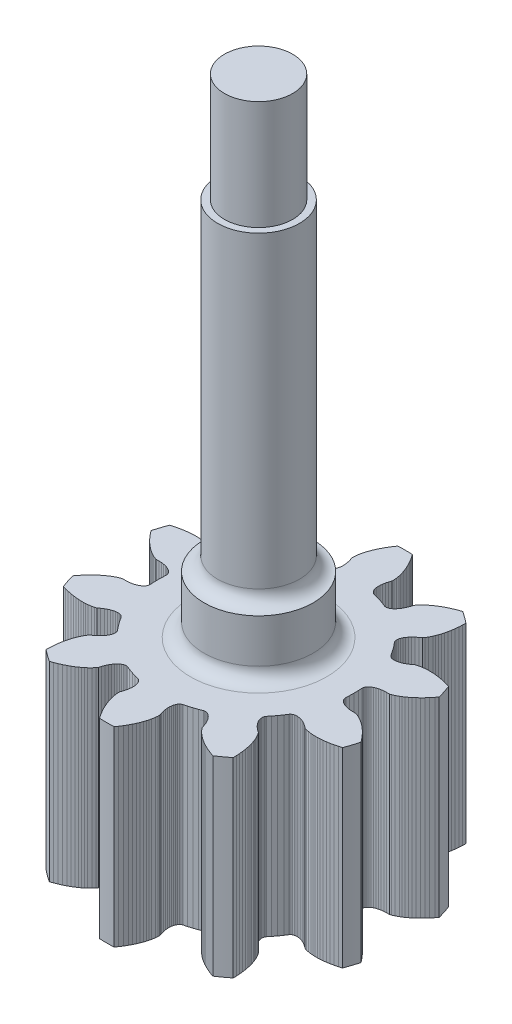
SolidWorks part; units mm, degrees
ref_plane "Front Plane" through (0, 0, 0) normal (0, 0, 1) x (1, 0, 0)
ref_plane "Top Plane" through (0, 0, 0) normal (0, 1, 0) x (1, 0, 0)
ref_plane "Right Plane" through (0, 0, 0) normal (1, 0, 0) x (0, 0, -1)
sketch "Sketch1" plane through (0, 0, 0) normal (0, 1, 0) x (1, 0, 0)
  circle A0 centre (0, 0) radius 2
  dimension "D1" = 4
extrude "Boss-Extrude1" add sketch "Sketch1" along normal blind 2.1
sketch "Sketch2" plane through (0, 2.1, 0) normal (0, 1, 0) x (1, 0, 0)
  circle A0 centre (0, 0) radius 1.5
  dimension "D1" = 3
extrude "Boss-Extrude3" add sketch "Sketch2" along normal blind 15.8
sketch "Sketch4" plane through (0, 0, 0) normal (0, -1, 0) x (1, 0, 0)
  line L0 (-3.5103, -4.1377) -> (-3.5022, -4.0065)
  line L1 (-3.5022, -4.0065) -> (-3.4891, -3.8807)
  line L2 (-3.4891, -3.8807) -> (-3.472, -3.7643)
  line L3 (-3.472, -3.7643) -> (-3.4515, -3.6564)
  line L4 (-3.4515, -3.6564) -> (-3.4282, -3.5564)
  line L5 (-3.4282, -3.5564) -> (-3.403, -3.4657)
  line L6 (-3.403, -3.4657) -> (-3.3761, -3.3825)
  line L7 (-3.3761, -3.3825) -> (-3.3483, -3.3075)
  line L8 (-3.3483, -3.3075) -> (-3.3202, -3.2404)
  line L9 (-3.3202, -3.2404) -> (-3.2664, -3.1313)
  line L10 (-3.2664, -3.1313) -> (-3.2183, -3.0513)
  line L11 (-3.2183, -3.0513) -> (-3.1781, -2.9961)
  line L12 (-3.1781, -2.9961) -> (-3.0986, -2.9414)
  line L13 (-3.0986, -2.9414) -> (-3.0227, -2.8808)
  line L14 (-3.0227, -2.8808) -> (-2.957, -2.8193)
  line L15 (-2.957, -2.8193) -> (-2.9016, -2.7578)
  line L16 (-2.9016, -2.7578) -> (-2.8562, -2.6969)
  line L17 (-2.8562, -2.6969) -> (-2.8208, -2.6373)
  line L18 (-2.8208, -2.6373) -> (-2.7951, -2.5799)
  line L19 (-2.7951, -2.5799) -> (-2.7789, -2.5252)
  line L20 (-2.7789, -2.5252) -> (-2.7718, -2.474)
  line L21 (-2.7718, -2.474) -> (-2.7736, -2.427)
  line L22 (-2.7736, -2.427) -> (-2.7838, -2.3847)
  line L23 (-2.7838, -2.3847) -> (-2.8021, -2.3479)
  line L24 (-2.8021, -2.3479) -> (-2.8109, -2.3356)
  line L25 (-2.8109, -2.3356) -> (-2.8974, -2.231)
  line L26 (-2.8974, -2.231) -> (-2.9943, -2.1036)
  line L27 (-2.9943, -2.1036) -> (-3.0855, -1.972)
  line L28 (-3.0855, -1.972) -> (-3.1583, -1.8575)
  line L29 (-3.1583, -1.8575) -> (-3.1673, -1.8453)
  line L30 (-3.1673, -1.8453) -> (-3.1967, -1.8165)
  line L31 (-3.1967, -1.8165) -> (-3.2337, -1.7937)
  line L32 (-3.2337, -1.7937) -> (-3.2779, -1.7775)
  line L33 (-3.2779, -1.7775) -> (-3.3287, -1.7684)
  line L34 (-3.3287, -1.7684) -> (-3.3857, -1.7669)
  line L35 (-3.3857, -1.7669) -> (-3.4483, -1.7736)
  line L36 (-3.4483, -1.7736) -> (-3.5159, -1.7889)
  line L37 (-3.5159, -1.7889) -> (-3.5879, -1.8132)
  line L38 (-3.5879, -1.8132) -> (-3.6635, -1.8469)
  line L39 (-3.6635, -1.8469) -> (-3.7423, -1.8903)
  line L40 (-3.7423, -1.8903) -> (-3.8234, -1.9438)
  line L41 (-3.8234, -1.9438) -> (-3.9, -2.0026)
  line L42 (-3.9, -2.0026) -> (-3.9648, -2.0237)
  line L43 (-3.9648, -2.0237) -> (-4.0558, -2.0448)
  line L44 (-4.0558, -2.0448) -> (-4.1762, -2.0622)
  line L45 (-4.1762, -2.0622) -> (-4.2487, -2.0682)
  line L46 (-4.2487, -2.0682) -> (-4.3286, -2.0714)
  line L47 (-4.3286, -2.0714) -> (-4.4161, -2.0713)
  line L48 (-4.4161, -2.0713) -> (-4.5101, -2.0673)
  line L49 (-4.5101, -2.0673) -> (-4.6124, -2.0586)
  line L50 (-4.6124, -2.0586) -> (-4.7214, -2.0447)
  line L51 (-4.7214, -2.0447) -> (-4.8374, -2.025)
  line L52 (-4.8374, -2.025) -> (-4.9611, -1.9985)
  line L53 (-4.9611, -1.9985) -> (-5.0883, -1.9657)
  line L54 (-5.0883, -1.9657) -> (-5.1999, -1.9322)
  line L55 (-5.3654, -1.4226) -> (-5.2949, -1.3299)
  line L56 (-5.2949, -1.3299) -> (-5.2112, -1.2286)
  line L57 (-5.2112, -1.2286) -> (-5.1267, -1.1345)
  line L58 (-5.1267, -1.1345) -> (-5.0445, -1.0503)
  line L59 (-5.0445, -1.0503) -> (-4.9645, -0.9751)
  line L60 (-4.9645, -0.9751) -> (-4.8868, -0.9079)
  line L61 (-4.8868, -0.9079) -> (-4.8131, -0.8494)
  line L62 (-4.8131, -0.8494) -> (-4.7424, -0.7978)
  line L63 (-4.7424, -0.7978) -> (-4.6759, -0.7535)
  line L64 (-4.6759, -0.7535) -> (-4.6137, -0.7157)
  line L65 (-4.6137, -0.7157) -> (-4.5061, -0.6591)
  line L66 (-4.5061, -0.6591) -> (-4.4201, -0.6226)
  line L67 (-4.4201, -0.6226) -> (-4.3552, -0.6016)
  line L68 (-4.3552, -0.6016) -> (-4.2587, -0.6041)
  line L69 (-4.2587, -0.6041) -> (-4.1616, -0.5997)
  line L70 (-4.1616, -0.5997) -> (-4.0724, -0.5886)
  line L71 (-4.0724, -0.5886) -> (-3.9914, -0.5713)
  line L72 (-3.9914, -0.5713) -> (-3.9189, -0.5487)
  line L73 (-3.9189, -0.5487) -> (-3.8552, -0.5213)
  line L74 (-3.8552, -0.5213) -> (-3.8007, -0.49)
  line L75 (-3.8007, -0.49) -> (-3.7554, -0.4553)
  line L76 (-3.7554, -0.4553) -> (-3.7196, -0.418)
  line L77 (-3.7196, -0.418) -> (-3.6934, -0.379)
  line L78 (-3.6934, -0.379) -> (-3.6768, -0.3388)
  line L79 (-3.6768, -0.3388) -> (-3.6699, -0.2982)
  line L80 (-3.6699, -0.2982) -> (-3.6699, -0.283)
  line L81 (-3.6699, -0.283) -> (-3.6783, -0.1476)
  line L82 (-3.6783, -0.1476) -> (-3.6819, 0.0124)
  line L83 (-3.6819, 0.0124) -> (-3.6783, 0.1725)
  line L84 (-3.6783, 0.1725) -> (-3.6699, 0.3079)
  line L85 (-3.6699, 0.3079) -> (-3.6699, 0.3231)
  line L86 (-3.6699, 0.3231) -> (-3.6768, 0.3636)
  line L87 (-3.6768, 0.3636) -> (-3.6934, 0.4038)
  line L88 (-3.6934, 0.4038) -> (-3.7196, 0.4429)
  line L89 (-3.7196, 0.4429) -> (-3.7554, 0.4802)
  line L90 (-3.7554, 0.4802) -> (-3.8007, 0.5149)
  line L91 (-3.8007, 0.5149) -> (-3.8552, 0.5462)
  line L92 (-3.8552, 0.5462) -> (-3.9189, 0.5736)
  line L93 (-3.9189, 0.5736) -> (-3.9914, 0.5962)
  line L94 (-3.9914, 0.5962) -> (-4.0724, 0.6134)
  line L95 (-4.0724, 0.6134) -> (-4.1616, 0.6246)
  line L96 (-4.1616, 0.6246) -> (-4.2587, 0.629)
  line L97 (-4.2587, 0.629) -> (-4.3552, 0.6265)
  line L98 (-4.3552, 0.6265) -> (-4.4201, 0.6475)
  line L99 (-4.4201, 0.6475) -> (-4.5061, 0.684)
  line L100 (-4.5061, 0.684) -> (-4.6137, 0.7406)
  line L101 (-4.6137, 0.7406) -> (-4.6759, 0.7784)
  line L102 (-4.6759, 0.7784) -> (-4.7424, 0.8227)
  line L103 (-4.7424, 0.8227) -> (-4.8131, 0.8742)
  line L104 (-4.8131, 0.8742) -> (-4.8868, 0.9328)
  line L105 (-4.8868, 0.9328) -> (-4.9645, 0.9999)
  line L106 (-4.9645, 0.9999) -> (-5.0445, 1.0752)
  line L107 (-5.0445, 1.0752) -> (-5.1267, 1.1594)
  line L108 (-5.1267, 1.1594) -> (-5.2112, 1.2535)
  line L109 (-5.2112, 1.2535) -> (-5.2949, 1.3548)
  line L110 (-5.2949, 1.3548) -> (-5.3654, 1.4475)
  line L111 (-5.1999, 1.957) -> (-5.0883, 1.9906)
  line L112 (-5.0883, 1.9906) -> (-4.9611, 2.0234)
  line L113 (-4.9611, 2.0234) -> (-4.8374, 2.0499)
  line L114 (-4.8374, 2.0499) -> (-4.7214, 2.0696)
  line L115 (-4.7214, 2.0696) -> (-4.6124, 2.0835)
  line L116 (-4.6124, 2.0835) -> (-4.5101, 2.0922)
  line L117 (-4.5101, 2.0922) -> (-4.4161, 2.0962)
  line L118 (-4.4161, 2.0962) -> (-4.3286, 2.0963)
  line L119 (-4.3286, 2.0963) -> (-4.2487, 2.0931)
  line L120 (-4.2487, 2.0931) -> (-4.1762, 2.0871)
  line L121 (-4.1762, 2.0871) -> (-4.0558, 2.0696)
  line L122 (-4.0558, 2.0696) -> (-3.9648, 2.0486)
  line L123 (-3.9648, 2.0486) -> (-3.9, 2.0274)
  line L124 (-3.9, 2.0274) -> (-3.8234, 1.9687)
  line L125 (-3.8234, 1.9687) -> (-3.7423, 1.9152)
  line L126 (-3.7423, 1.9152) -> (-3.6635, 1.8718)
  line L127 (-3.6635, 1.8718) -> (-3.5879, 1.8381)
  line L128 (-3.5879, 1.8381) -> (-3.5159, 1.8138)
  line L129 (-3.5159, 1.8138) -> (-3.4483, 1.7985)
  line L130 (-3.4483, 1.7985) -> (-3.3857, 1.7918)
  line L131 (-3.3857, 1.7918) -> (-3.3287, 1.7933)
  line L132 (-3.3287, 1.7933) -> (-3.2779, 1.8024)
  line L133 (-3.2779, 1.8024) -> (-3.2337, 1.8186)
  line L134 (-3.2337, 1.8186) -> (-3.1967, 1.8414)
  line L135 (-3.1967, 1.8414) -> (-3.1673, 1.8702)
  line L136 (-3.1673, 1.8702) -> (-3.1583, 1.8824)
  line L137 (-3.1583, 1.8824) -> (-3.0855, 1.9969)
  line L138 (-3.0855, 1.9969) -> (-2.9943, 2.1285)
  line L139 (-2.9943, 2.1285) -> (-2.8974, 2.2559)
  line L140 (-2.8974, 2.2559) -> (-2.8109, 2.3605)
  line L141 (-2.8109, 2.3605) -> (-2.8021, 2.3728)
  line L142 (-2.8021, 2.3728) -> (-2.7838, 2.4096)
  line L143 (-2.7838, 2.4096) -> (-2.7736, 2.4519)
  line L144 (-2.7736, 2.4519) -> (-2.7718, 2.4989)
  line L145 (-2.7718, 2.4989) -> (-2.7789, 2.5501)
  line L146 (-2.7789, 2.5501) -> (-2.7951, 2.6048)
  line L147 (-2.7951, 2.6048) -> (-2.8208, 2.6622)
  line L148 (-2.8208, 2.6622) -> (-2.8562, 2.7218)
  line L149 (-2.8562, 2.7218) -> (-2.9016, 2.7827)
  line L150 (-2.9016, 2.7827) -> (-2.957, 2.8442)
  line L151 (-2.957, 2.8442) -> (-3.0227, 2.9057)
  line L152 (-3.0227, 2.9057) -> (-3.0986, 2.9663)
  line L153 (-3.0986, 2.9663) -> (-3.1781, 3.021)
  line L154 (-3.1781, 3.021) -> (-3.2183, 3.0762)
  line L155 (-3.2183, 3.0762) -> (-3.2664, 3.1562)
  line L156 (-3.2664, 3.1562) -> (-3.3202, 3.2653)
  line L157 (-3.3202, 3.2653) -> (-3.3483, 3.3324)
  line L158 (-3.3483, 3.3324) -> (-3.3761, 3.4074)
  line L159 (-3.3761, 3.4074) -> (-3.403, 3.4906)
  line L160 (-3.403, 3.4906) -> (-3.4282, 3.5812)
  line L161 (-3.4282, 3.5812) -> (-3.4515, 3.6813)
  line L162 (-3.4515, 3.6813) -> (-3.472, 3.7892)
  line L163 (-3.472, 3.7892) -> (-3.4891, 3.9056)
  line L164 (-3.4891, 3.9056) -> (-3.5022, 4.0314)
  line L165 (-3.5022, 4.0314) -> (-3.5103, 4.1625)
  line L166 (-3.5103, 4.1625) -> (-3.5128, 4.279)
  line L167 (-3.0794, 4.5939) -> (-2.9694, 4.5555)
  line L168 (-2.9694, 4.5555) -> (-2.8472, 4.5073)
  line L169 (-2.8472, 4.5073) -> (-2.7316, 4.456)
  line L170 (-2.7316, 4.456) -> (-2.6261, 4.4037)
  line L171 (-2.6261, 4.4037) -> (-2.5298, 4.3509)
  line L172 (-2.5298, 4.3509) -> (-2.4419, 4.2978)
  line L173 (-2.4419, 4.2978) -> (-2.3635, 4.2458)
  line L174 (-2.3635, 4.2458) -> (-2.2927, 4.1945)
  line L175 (-2.2927, 4.1945) -> (-2.23, 4.1449)
  line L176 (-2.23, 4.1449) -> (-2.1748, 4.0974)
  line L177 (-2.1748, 4.0974) -> (-2.0877, 4.0126)
  line L178 (-2.0877, 4.0126) -> (-2.0264, 3.9421)
  line L179 (-2.0264, 3.9421) -> (-1.9864, 3.8869)
  line L180 (-1.9864, 3.8869) -> (-1.9589, 3.7943)
  line L181 (-1.9589, 3.7943) -> (-1.9248, 3.7034)
  line L182 (-1.9248, 3.7034) -> (-1.8866, 3.6219)
  line L183 (-1.8866, 3.6219) -> (-1.8452, 3.5502)
  line L184 (-1.8452, 3.5502) -> (-1.8012, 3.4883)
  line L185 (-1.8012, 3.4883) -> (-1.7556, 3.4362)
  line L186 (-1.7556, 3.4362) -> (-1.7089, 3.394)
  line L187 (-1.7089, 3.394) -> (-1.6619, 3.3616)
  line L188 (-1.6619, 3.3616) -> (-1.6154, 3.3391)
  line L189 (-1.6154, 3.3391) -> (-1.5701, 3.3262)
  line L190 (-1.5701, 3.3262) -> (-1.5268, 3.3229)
  line L191 (-1.5268, 3.3229) -> (-1.4861, 3.3289)
  line L192 (-1.4861, 3.3289) -> (-1.4716, 3.3335)
  line L193 (-1.4716, 3.3335) -> (-1.3455, 3.3834)
  line L194 (-1.3455, 3.3834) -> (-1.1943, 3.4362)
  line L195 (-1.1943, 3.4362) -> (-1.041, 3.4823)
  line L196 (-1.041, 3.4823) -> (-0.9096, 3.5161)
  line L197 (-0.9096, 3.5161) -> (-0.8952, 3.5209)
  line L198 (-0.8952, 3.5209) -> (-0.8588, 3.54)
  line L199 (-0.8588, 3.54) -> (-0.8256, 3.5681)
  line L200 (-0.8256, 3.5681) -> (-0.7966, 3.6051)
  line L201 (-0.7966, 3.6051) -> (-0.7722, 3.6507)
  line L202 (-0.7722, 3.6507) -> (-0.7532, 3.7045)
  line L203 (-0.7532, 3.7045) -> (-0.7402, 3.7661)
  line L204 (-0.7402, 3.7661) -> (-0.7339, 3.8351)
  line L205 (-0.7339, 3.8351) -> (-0.7348, 3.911)
  line L206 (-0.7348, 3.911) -> (-0.7434, 3.9934)
  line L207 (-0.7434, 3.9934) -> (-0.7604, 4.0817)
  line L208 (-0.7604, 4.0817) -> (-0.7862, 4.1753)
  line L209 (-0.7862, 4.1753) -> (-0.8184, 4.2664)
  line L210 (-0.8184, 4.2664) -> (-0.8185, 4.3346)
  line L211 (-0.8185, 4.3346) -> (-0.8104, 4.4276)
  line L212 (-0.8104, 4.4276) -> (-0.7898, 4.5475)
  line L213 (-0.7898, 4.5475) -> (-0.773, 4.6183)
  line L214 (-0.773, 4.6183) -> (-0.7514, 4.6953)
  line L215 (-0.7514, 4.6953) -> (-0.7243, 4.7785)
  line L216 (-0.7243, 4.7785) -> (-0.6914, 4.8666)
  line L217 (-0.6914, 4.8666) -> (-0.6515, 4.9612)
  line L218 (-0.6515, 4.9612) -> (-0.6047, 5.0605)
  line L219 (-0.6047, 5.0605) -> (-0.55, 5.1648)
  line L220 (-0.55, 5.1648) -> (-0.4867, 5.2743)
  line L221 (-0.4867, 5.2743) -> (-0.4161, 5.3851)
  line L222 (-0.4161, 5.3851) -> (-0.3498, 5.4809)
  line L223 (0.186, 5.4809) -> (0.2524, 5.3851)
  line L224 (0.2524, 5.3851) -> (0.3229, 5.2743)
  line L225 (0.3229, 5.2743) -> (0.3863, 5.1648)
  line L226 (0.3863, 5.1648) -> (0.4409, 5.0605)
  line L227 (0.4409, 5.0605) -> (0.4878, 4.9612)
  line L228 (0.4878, 4.9612) -> (0.5277, 4.8666)
  line L229 (0.5277, 4.8666) -> (0.5605, 4.7785)
  line L230 (0.5605, 4.7785) -> (0.5877, 4.6953)
  line L231 (0.5877, 4.6953) -> (0.6093, 4.6183)
  line L232 (0.6093, 4.6183) -> (0.626, 4.5475)
  line L233 (0.626, 4.5475) -> (0.6466, 4.4276)
  line L234 (0.6466, 4.4276) -> (0.6547, 4.3346)
  line L235 (0.6547, 4.3346) -> (0.6546, 4.2664)
  line L236 (0.6546, 4.2664) -> (0.6224, 4.1753)
  line L237 (0.6224, 4.1753) -> (0.5967, 4.0817)
  line L238 (0.5967, 4.0817) -> (0.5797, 3.9934)
  line L239 (0.5797, 3.9934) -> (0.571, 3.911)
  line L240 (0.571, 3.911) -> (0.5702, 3.8351)
  line L241 (0.5702, 3.8351) -> (0.5765, 3.7661)
  line L242 (0.5765, 3.7661) -> (0.5895, 3.7045)
  line L243 (0.5895, 3.7045) -> (0.6085, 3.6507)
  line L244 (0.6085, 3.6507) -> (0.6328, 3.6051)
  line L245 (0.6328, 3.6051) -> (0.6619, 3.5681)
  line L246 (0.6619, 3.5681) -> (0.695, 3.54)
  line L247 (0.695, 3.54) -> (0.7315, 3.5209)
  line L248 (0.7315, 3.5209) -> (0.7459, 3.5161)
  line L249 (0.7459, 3.5161) -> (0.8773, 3.4823)
  line L250 (0.8773, 3.4823) -> (1.0306, 3.4362)
  line L251 (1.0306, 3.4362) -> (1.1817, 3.3834)
  line L252 (1.1817, 3.3834) -> (1.3079, 3.3335)
  line L253 (1.3079, 3.3335) -> (1.3223, 3.3289)
  line L254 (1.3223, 3.3289) -> (1.363, 3.3229)
  line L255 (1.363, 3.3229) -> (1.4064, 3.3262)
  line L256 (1.4064, 3.3262) -> (1.4517, 3.3391)
  line L257 (1.4517, 3.3391) -> (1.4982, 3.3616)
  line L258 (1.4982, 3.3616) -> (1.5451, 3.394)
  line L259 (1.5451, 3.394) -> (1.5918, 3.4362)
  line L260 (1.5918, 3.4362) -> (1.6375, 3.4883)
  line L261 (1.6375, 3.4883) -> (1.6814, 3.5502)
  line L262 (1.6814, 3.5502) -> (1.7229, 3.6219)
  line L263 (1.7229, 3.6219) -> (1.761, 3.7034)
  line L264 (1.761, 3.7034) -> (1.7952, 3.7943)
  line L265 (1.7952, 3.7943) -> (1.8227, 3.8869)
  line L266 (1.8227, 3.8869) -> (1.8627, 3.9421)
  line L267 (1.8627, 3.9421) -> (1.9239, 4.0126)
  line L268 (1.9239, 4.0126) -> (2.0111, 4.0974)
  line L269 (2.0111, 4.0974) -> (2.0662, 4.1449)
  line L270 (2.0662, 4.1449) -> (2.1289, 4.1945)
  line L271 (2.1289, 4.1945) -> (2.1998, 4.2458)
  line L272 (2.1998, 4.2458) -> (2.2782, 4.2978)
  line L273 (2.2782, 4.2978) -> (2.3661, 4.3509)
  line L274 (2.3661, 4.3509) -> (2.4624, 4.4037)
  line L275 (2.4624, 4.4037) -> (2.5679, 4.456)
  line L276 (2.5679, 4.456) -> (2.6835, 4.5073)
  line L277 (2.6835, 4.5073) -> (2.8057, 4.5555)
  line L278 (2.8057, 4.5555) -> (2.9157, 4.5939)
  line L279 (3.3491, 4.279) -> (3.3465, 4.1625)
  line L280 (3.3465, 4.1625) -> (3.3384, 4.0314)
  line L281 (3.3384, 4.0314) -> (3.3254, 3.9056)
  line L282 (3.3254, 3.9056) -> (3.3083, 3.7892)
  line L283 (3.3083, 3.7892) -> (3.2878, 3.6813)
  line L284 (3.2878, 3.6813) -> (3.2644, 3.5812)
  line L285 (3.2644, 3.5812) -> (3.2392, 3.4906)
  line L286 (3.2392, 3.4906) -> (3.2123, 3.4074)
  line L287 (3.2123, 3.4074) -> (3.1846, 3.3324)
  line L288 (3.1846, 3.3324) -> (3.1564, 3.2653)
  line L289 (3.1564, 3.2653) -> (3.1027, 3.1562)
  line L290 (3.1027, 3.1562) -> (3.0545, 3.0762)
  line L291 (3.0545, 3.0762) -> (3.0144, 3.021)
  line L292 (3.0144, 3.021) -> (2.9348, 2.9663)
  line L293 (2.9348, 2.9663) -> (2.8589, 2.9057)
  line L294 (2.8589, 2.9057) -> (2.7933, 2.8442)
  line L295 (2.7933, 2.8442) -> (2.7378, 2.7827)
  line L296 (2.7378, 2.7827) -> (2.6925, 2.7218)
  line L297 (2.6925, 2.7218) -> (2.6571, 2.6622)
  line L298 (2.6571, 2.6622) -> (2.6314, 2.6048)
  line L299 (2.6314, 2.6048) -> (2.6151, 2.5501)
  line L300 (2.6151, 2.5501) -> (2.6081, 2.4989)
  line L301 (2.6081, 2.4989) -> (2.6098, 2.4519)
  line L302 (2.6098, 2.4519) -> (2.6201, 2.4096)
  line L303 (2.6201, 2.4096) -> (2.6384, 2.3728)
  line L304 (2.6384, 2.3728) -> (2.6472, 2.3605)
  line L305 (2.6472, 2.3605) -> (2.7336, 2.2559)
  line L306 (2.7336, 2.2559) -> (2.8306, 2.1285)
  line L307 (2.8306, 2.1285) -> (2.9218, 1.9969)
  line L308 (2.9218, 1.9969) -> (2.9946, 1.8824)
  line L309 (2.9946, 1.8824) -> (3.0035, 1.8702)
  line L310 (3.0035, 1.8702) -> (3.0329, 1.8414)
  line L311 (3.0329, 1.8414) -> (3.0699, 1.8186)
  line L312 (3.0699, 1.8186) -> (3.1141, 1.8024)
  line L313 (3.1141, 1.8024) -> (3.165, 1.7933)
  line L314 (3.165, 1.7933) -> (3.222, 1.7918)
  line L315 (3.222, 1.7918) -> (3.2846, 1.7985)
  line L316 (3.2846, 1.7985) -> (3.3522, 1.8138)
  line L317 (3.3522, 1.8138) -> (3.4241, 1.8381)
  line L318 (3.4241, 1.8381) -> (3.4998, 1.8718)
  line L319 (3.4998, 1.8718) -> (3.5785, 1.9152)
  line L320 (3.5785, 1.9152) -> (3.6596, 1.9687)
  line L321 (3.6596, 1.9687) -> (3.7362, 2.0274)
  line L322 (3.7362, 2.0274) -> (3.8011, 2.0486)
  line L323 (3.8011, 2.0486) -> (3.8921, 2.0696)
  line L324 (3.8921, 2.0696) -> (4.0124, 2.0871)
  line L325 (4.0124, 2.0871) -> (4.085, 2.0931)
  line L326 (4.085, 2.0931) -> (4.1649, 2.0963)
  line L327 (4.1649, 2.0963) -> (4.2524, 2.0962)
  line L328 (4.2524, 2.0962) -> (4.3463, 2.0922)
  line L329 (4.3463, 2.0922) -> (4.4487, 2.0835)
  line L330 (4.4487, 2.0835) -> (4.5576, 2.0696)
  line L331 (4.5576, 2.0696) -> (4.6736, 2.0499)
  line L332 (4.6736, 2.0499) -> (4.7973, 2.0234)
  line L333 (4.7973, 2.0234) -> (4.9245, 1.9906)
  line L334 (4.9245, 1.9906) -> (5.0361, 1.957)
  line L335 (5.2017, 1.4475) -> (5.1311, 1.3548)
  line L336 (5.1311, 1.3548) -> (5.0475, 1.2535)
  line L337 (5.0475, 1.2535) -> (4.963, 1.1594)
  line L338 (4.963, 1.1594) -> (4.8807, 1.0752)
  line L339 (4.8807, 1.0752) -> (4.8007, 0.9999)
  line L340 (4.8007, 0.9999) -> (4.723, 0.9328)
  line L341 (4.723, 0.9328) -> (4.6494, 0.8742)
  line L342 (4.6494, 0.8742) -> (4.5787, 0.8227)
  line L343 (4.5787, 0.8227) -> (4.5122, 0.7784)
  line L344 (4.5122, 0.7784) -> (4.4499, 0.7406)
  line L345 (4.4499, 0.7406) -> (4.3423, 0.684)
  line L346 (4.3423, 0.684) -> (4.2563, 0.6475)
  line L347 (4.2563, 0.6475) -> (4.1914, 0.6265)
  line L348 (4.1914, 0.6265) -> (4.0949, 0.629)
  line L349 (4.0949, 0.629) -> (3.9979, 0.6246)
  line L350 (3.9979, 0.6246) -> (3.9087, 0.6134)
  line L351 (3.9087, 0.6134) -> (3.8276, 0.5962)
  line L352 (3.8276, 0.5962) -> (3.7551, 0.5736)
  line L353 (3.7551, 0.5736) -> (3.6915, 0.5462)
  line L354 (3.6915, 0.5462) -> (3.6369, 0.5149)
  line L355 (3.6369, 0.5149) -> (3.5916, 0.4802)
  line L356 (3.5916, 0.4802) -> (3.5558, 0.4429)
  line L357 (3.5558, 0.4429) -> (3.5296, 0.4038)
  line L358 (3.5296, 0.4038) -> (3.5131, 0.3636)
  line L359 (3.5131, 0.3636) -> (3.5062, 0.3231)
  line L360 (3.5062, 0.3231) -> (3.5061, 0.3079)
  line L361 (3.5061, 0.3079) -> (3.5146, 0.1725)
  line L362 (3.5146, 0.1725) -> (3.5181, 0.0124)
  line L363 (3.5181, 0.0124) -> (3.5146, -0.1476)
  line L364 (3.5146, -0.1476) -> (3.5061, -0.283)
  line L365 (3.5061, -0.283) -> (3.5062, -0.2982)
  line L366 (3.5062, -0.2982) -> (3.5131, -0.3388)
  line L367 (3.5131, -0.3388) -> (3.5296, -0.379)
  line L368 (3.5296, -0.379) -> (3.5558, -0.418)
  line L369 (3.5558, -0.418) -> (3.5916, -0.4553)
  line L370 (3.5916, -0.4553) -> (3.6369, -0.49)
  line L371 (3.6369, -0.49) -> (3.6915, -0.5213)
  line L372 (3.6915, -0.5213) -> (3.7551, -0.5487)
  line L373 (3.7551, -0.5487) -> (3.8276, -0.5713)
  line L374 (3.8276, -0.5713) -> (3.9087, -0.5886)
  line L375 (3.9087, -0.5886) -> (3.9979, -0.5997)
  line L376 (3.9979, -0.5997) -> (4.0949, -0.6041)
  line L377 (4.0949, -0.6041) -> (4.1914, -0.6016)
  line L378 (4.1914, -0.6016) -> (4.2563, -0.6226)
  line L379 (4.2563, -0.6226) -> (4.3423, -0.6591)
  line L380 (4.3423, -0.6591) -> (4.4499, -0.7157)
  line L381 (4.4499, -0.7157) -> (4.5122, -0.7535)
  line L382 (4.5122, -0.7535) -> (4.5787, -0.7978)
  line L383 (4.5787, -0.7978) -> (4.6494, -0.8494)
  line L384 (4.6494, -0.8494) -> (4.723, -0.9079)
  line L385 (4.723, -0.9079) -> (4.8007, -0.9751)
  line L386 (4.8007, -0.9751) -> (4.8807, -1.0503)
  line L387 (4.8807, -1.0503) -> (4.963, -1.1345)
  line L388 (4.963, -1.1345) -> (5.0475, -1.2286)
  line L389 (5.0475, -1.2286) -> (5.1311, -1.3299)
  line L390 (5.1311, -1.3299) -> (5.2017, -1.4226)
  line L391 (5.0361, -1.9322) -> (4.9245, -1.9657)
  line L392 (4.9245, -1.9657) -> (4.7973, -1.9985)
  line L393 (4.7973, -1.9985) -> (4.6736, -2.025)
  line L394 (4.6736, -2.025) -> (4.5576, -2.0447)
  line L395 (4.5576, -2.0447) -> (4.4487, -2.0586)
  line L396 (4.4487, -2.0586) -> (4.3463, -2.0673)
  line L397 (4.3463, -2.0673) -> (4.2524, -2.0713)
  line L398 (4.2524, -2.0713) -> (4.1649, -2.0714)
  line L399 (4.1649, -2.0714) -> (4.085, -2.0682)
  line L400 (4.085, -2.0682) -> (4.0124, -2.0622)
  line L401 (4.0124, -2.0622) -> (3.8921, -2.0448)
  line L402 (3.8921, -2.0448) -> (3.8011, -2.0237)
  line L403 (3.8011, -2.0237) -> (3.7362, -2.0026)
  line L404 (3.7362, -2.0026) -> (3.6596, -1.9438)
  line L405 (3.6596, -1.9438) -> (3.5785, -1.8903)
  line L406 (3.5785, -1.8903) -> (3.4998, -1.8469)
  line L407 (3.4998, -1.8469) -> (3.4241, -1.8132)
  line L408 (3.4241, -1.8132) -> (3.3522, -1.7889)
  line L409 (3.3522, -1.7889) -> (3.2846, -1.7736)
  line L410 (3.2846, -1.7736) -> (3.222, -1.7669)
  line L411 (3.222, -1.7669) -> (3.165, -1.7684)
  line L412 (3.165, -1.7684) -> (3.1141, -1.7775)
  line L413 (3.1141, -1.7775) -> (3.0699, -1.7937)
  line L414 (3.0699, -1.7937) -> (3.0329, -1.8165)
  line L415 (3.0329, -1.8165) -> (3.0035, -1.8453)
  line L416 (3.0035, -1.8453) -> (2.9946, -1.8575)
  line L417 (2.9946, -1.8575) -> (2.9218, -1.972)
  line L418 (2.9218, -1.972) -> (2.8306, -2.1036)
  line L419 (2.8306, -2.1036) -> (2.7336, -2.231)
  line L840 (2.7336, -2.231) -> (2.6472, -2.3356)
  line L841 (2.6472, -2.3356) -> (2.6384, -2.3479)
  line L842 (2.6384, -2.3479) -> (2.6201, -2.3847)
  line L843 (2.6201, -2.3847) -> (2.6098, -2.427)
  line L844 (2.6098, -2.427) -> (2.6081, -2.474)
  line L845 (2.6081, -2.474) -> (2.6151, -2.5252)
  line L846 (2.6151, -2.5252) -> (2.6314, -2.5799)
  line L847 (2.6314, -2.5799) -> (2.6571, -2.6373)
  line L848 (2.6571, -2.6373) -> (2.6925, -2.6969)
  line L849 (2.6925, -2.6969) -> (2.7378, -2.7578)
  line L850 (2.7378, -2.7578) -> (2.7933, -2.8193)
  line L851 (2.7933, -2.8193) -> (2.8589, -2.8808)
  line L852 (2.8589, -2.8808) -> (2.9348, -2.9414)
  line L853 (2.9348, -2.9414) -> (3.0144, -2.9961)
  line L854 (3.0144, -2.9961) -> (3.0545, -3.0513)
  line L855 (3.0545, -3.0513) -> (3.1027, -3.1313)
  line L856 (3.1027, -3.1313) -> (3.1564, -3.2404)
  line L857 (3.1564, -3.2404) -> (3.1846, -3.3075)
  line L858 (3.1846, -3.3075) -> (3.2123, -3.3825)
  line L859 (3.2123, -3.3825) -> (3.2392, -3.4657)
  line L860 (3.2392, -3.4657) -> (3.2644, -3.5564)
  line L861 (3.2644, -3.5564) -> (3.2878, -3.6564)
  line L862 (3.2878, -3.6564) -> (3.3083, -3.7643)
  line L863 (3.3083, -3.7643) -> (3.3254, -3.8807)
  line L864 (3.3254, -3.8807) -> (3.3384, -4.0065)
  line L865 (3.3384, -4.0065) -> (3.3465, -4.1377)
  line L866 (3.3465, -4.1377) -> (3.3491, -4.2541)
  line L867 (2.9157, -4.569) -> (2.8057, -4.5306)
  line L868 (2.8057, -4.5306) -> (2.6835, -4.4824)
  line L869 (2.6835, -4.4824) -> (2.5679, -4.4311)
  line L870 (2.5679, -4.4311) -> (2.4624, -4.3788)
  line L871 (2.4624, -4.3788) -> (2.3661, -4.326)
  line L872 (2.3661, -4.326) -> (2.2782, -4.2729)
  line L873 (2.2782, -4.2729) -> (2.1998, -4.2209)
  line L874 (2.1998, -4.2209) -> (2.1289, -4.1696)
  line L875 (2.1289, -4.1696) -> (2.0662, -4.12)
  line L876 (2.0662, -4.12) -> (2.0111, -4.0725)
  line L877 (2.0111, -4.0725) -> (1.9239, -3.9877)
  line L878 (1.9239, -3.9877) -> (1.8627, -3.9172)
  line L879 (1.8627, -3.9172) -> (1.8227, -3.862)
  line L880 (1.8227, -3.862) -> (1.7952, -3.7694)
  line L881 (1.7952, -3.7694) -> (1.761, -3.6785)
  line L882 (1.761, -3.6785) -> (1.7229, -3.5971)
  line L883 (1.7229, -3.5971) -> (1.6814, -3.5253)
  line L884 (1.6814, -3.5253) -> (1.6375, -3.4634)
  line L885 (1.6375, -3.4634) -> (1.5918, -3.4113)
  line L886 (1.5918, -3.4113) -> (1.5451, -3.3691)
  line L887 (1.5451, -3.3691) -> (1.4982, -3.3367)
  line L888 (1.4982, -3.3367) -> (1.4517, -3.3142)
  line L889 (1.4517, -3.3142) -> (1.4064, -3.3013)
  line L890 (1.4064, -3.3013) -> (1.363, -3.298)
  line L891 (1.363, -3.298) -> (1.3223, -3.304)
  line L892 (1.3223, -3.304) -> (1.3079, -3.3086)
  line L893 (1.3079, -3.3086) -> (1.1817, -3.3585)
  line L894 (1.1817, -3.3585) -> (1.0306, -3.4114)
  line L895 (1.0306, -3.4114) -> (0.8773, -3.4574)
  line L896 (0.8773, -3.4574) -> (0.7459, -3.4913)
  line L897 (0.7459, -3.4913) -> (0.7315, -3.496)
  line L898 (0.7315, -3.496) -> (0.695, -3.5151)
  line L899 (0.695, -3.5151) -> (0.6619, -3.5432)
  line L900 (0.6619, -3.5432) -> (0.6328, -3.5802)
  line L901 (0.6328, -3.5802) -> (0.6085, -3.6258)
  line L902 (0.6085, -3.6258) -> (0.5895, -3.6796)
  line L903 (0.5895, -3.6796) -> (0.5765, -3.7412)
  line L904 (0.5765, -3.7412) -> (0.5702, -3.8102)
  line L905 (0.5702, -3.8102) -> (0.571, -3.8861)
  line L906 (0.571, -3.8861) -> (0.5797, -3.9685)
  line L907 (0.5797, -3.9685) -> (0.5967, -4.0568)
  line L908 (0.5967, -4.0568) -> (0.6224, -4.1504)
  line L909 (0.6224, -4.1504) -> (0.6546, -4.2415)
  line L910 (0.6546, -4.2415) -> (0.6547, -4.3097)
  line L911 (0.6547, -4.3097) -> (0.6466, -4.4027)
  line L912 (0.6466, -4.4027) -> (0.626, -4.5226)
  line L913 (0.626, -4.5226) -> (0.6093, -4.5934)
  line L914 (0.6093, -4.5934) -> (0.5877, -4.6704)
  line L915 (0.5877, -4.6704) -> (0.5605, -4.7536)
  line L916 (0.5605, -4.7536) -> (0.5277, -4.8417)
  line L917 (0.5277, -4.8417) -> (0.4878, -4.9363)
  line L918 (0.4878, -4.9363) -> (0.4409, -5.0357)
  line L919 (0.4409, -5.0357) -> (0.3863, -5.1399)
  line L920 (0.3863, -5.1399) -> (0.3229, -5.2494)
  line L921 (0.3229, -5.2494) -> (0.2524, -5.3602)
  line L922 (0.2524, -5.3602) -> (0.186, -5.456)
  line L923 (-0.3498, -5.456) -> (-0.4161, -5.3602)
  line L924 (-0.4161, -5.3602) -> (-0.4867, -5.2494)
  line L925 (-0.4867, -5.2494) -> (-0.55, -5.1399)
  line L926 (-0.55, -5.1399) -> (-0.6047, -5.0357)
  line L927 (-0.6047, -5.0357) -> (-0.6515, -4.9363)
  line L928 (-0.6515, -4.9363) -> (-0.6914, -4.8417)
  line L929 (-0.6914, -4.8417) -> (-0.7243, -4.7536)
  line L930 (-0.7243, -4.7536) -> (-0.7514, -4.6704)
  line L931 (-0.7514, -4.6704) -> (-0.773, -4.5934)
  line L932 (-0.773, -4.5934) -> (-0.7898, -4.5226)
  line L933 (-0.7898, -4.5226) -> (-0.8104, -4.4027)
  line L934 (-0.8104, -4.4027) -> (-0.8185, -4.3097)
  line L935 (-0.8185, -4.3097) -> (-0.8184, -4.2415)
  line L936 (-0.8184, -4.2415) -> (-0.7862, -4.1504)
  line L937 (-0.7862, -4.1504) -> (-0.7604, -4.0568)
  line L938 (-0.7604, -4.0568) -> (-0.7434, -3.9685)
  line L939 (-0.7434, -3.9685) -> (-0.7348, -3.8861)
  line L940 (-0.7348, -3.8861) -> (-0.7339, -3.8102)
  line L941 (-0.7339, -3.8102) -> (-0.7402, -3.7412)
  line L942 (-0.7402, -3.7412) -> (-0.7532, -3.6796)
  line L943 (-0.7532, -3.6796) -> (-0.7722, -3.6258)
  line L944 (-0.7722, -3.6258) -> (-0.7966, -3.5802)
  line L945 (-0.7966, -3.5802) -> (-0.8256, -3.5432)
  line L946 (-0.8256, -3.5432) -> (-0.8588, -3.5151)
  line L947 (-0.8588, -3.5151) -> (-0.8952, -3.496)
  line L948 (-0.8952, -3.496) -> (-0.9096, -3.4913)
  line L949 (-0.9096, -3.4913) -> (-1.041, -3.4574)
  line L950 (-1.041, -3.4574) -> (-1.1943, -3.4114)
  line L951 (-1.1943, -3.4114) -> (-1.3455, -3.3585)
  line L952 (-1.3455, -3.3585) -> (-1.4716, -3.3086)
  line L953 (-1.4716, -3.3086) -> (-1.4861, -3.304)
  line L954 (-1.4861, -3.304) -> (-1.5268, -3.298)
  line L955 (-1.5268, -3.298) -> (-1.5701, -3.3013)
  line L956 (-1.5701, -3.3013) -> (-1.6154, -3.3142)
  line L957 (-1.6154, -3.3142) -> (-1.6619, -3.3367)
  line L958 (-1.6619, -3.3367) -> (-1.7089, -3.3691)
  line L959 (-1.7089, -3.3691) -> (-1.7556, -3.4113)
  line L960 (-1.7556, -3.4113) -> (-1.8012, -3.4634)
  line L961 (-1.8012, -3.4634) -> (-1.8452, -3.5253)
  line L962 (-1.8452, -3.5253) -> (-1.8866, -3.5971)
  line L963 (-1.8866, -3.5971) -> (-1.9248, -3.6785)
  line L964 (-1.9248, -3.6785) -> (-1.9589, -3.7694)
  line L965 (-1.9589, -3.7694) -> (-1.9864, -3.862)
  line L966 (-1.9864, -3.862) -> (-2.0264, -3.9172)
  line L967 (-2.0264, -3.9172) -> (-2.0877, -3.9877)
  line L968 (-2.0877, -3.9877) -> (-2.1748, -4.0725)
  line L969 (-2.1748, -4.0725) -> (-2.23, -4.12)
  line L970 (-2.23, -4.12) -> (-2.2927, -4.1696)
  line L971 (-2.2927, -4.1696) -> (-2.3635, -4.2209)
  line L972 (-2.3635, -4.2209) -> (-2.4419, -4.2729)
  line L973 (-2.4419, -4.2729) -> (-2.5298, -4.326)
  line L974 (-2.5298, -4.326) -> (-2.6261, -4.3788)
  line L975 (-2.6261, -4.3788) -> (-2.7316, -4.4311)
  line L976 (-2.7316, -4.4311) -> (-2.8472, -4.4824)
  line L977 (-2.8472, -4.4824) -> (-2.9694, -4.5306)
  line L978 (-2.9694, -4.5306) -> (-3.0794, -4.569)
  line L979 (-3.5128, -4.2541) -> (-3.5103, -4.1377)
  line L980 (-3.5103, -4.1377) -> (-3.5022, -4.0065)
  line L981 (-3.5022, -4.0065) -> (-3.4891, -3.8807)
  line L982 (-3.4891, -3.8807) -> (-3.472, -3.7643)
  line L983 (-3.472, -3.7643) -> (-3.4515, -3.6564)
  line L984 (-3.4515, -3.6564) -> (-3.4282, -3.5564)
  line L985 (-3.4282, -3.5564) -> (-3.403, -3.4657)
  line L986 (-3.403, -3.4657) -> (-3.3761, -3.3825)
  line L987 (-3.3761, -3.3825) -> (-3.3483, -3.3075)
  line L988 (-3.3483, -3.3075) -> (-3.3202, -3.2404)
  line L989 (-3.3202, -3.2404) -> (-3.2664, -3.1313)
  line L990 (-3.2664, -3.1313) -> (-3.2183, -3.0513)
  line L991 (-3.2183, -3.0513) -> (-3.1781, -2.9961)
  line L992 (-3.1781, -2.9961) -> (-3.0986, -2.9414)
  line L993 (-3.0986, -2.9414) -> (-3.0227, -2.8808)
  line L994 (-3.0227, -2.8808) -> (-2.957, -2.8193)
  line L995 (-2.957, -2.8193) -> (-2.9016, -2.7578)
  line L996 (-2.9016, -2.7578) -> (-2.8562, -2.6969)
  line L997 (-2.8562, -2.6969) -> (-2.8208, -2.6373)
  line L998 (-2.8208, -2.6373) -> (-2.7951, -2.5799)
  line L999 (-2.7951, -2.5799) -> (-2.7789, -2.5252)
  line L1000 (-2.7789, -2.5252) -> (-2.7718, -2.474)
  line L1001 (-2.7718, -2.474) -> (-2.7736, -2.427)
  line L1002 (-2.7736, -2.427) -> (-2.7838, -2.3847)
  line L1003 (-2.7838, -2.3847) -> (-2.8021, -2.3479)
  line L1004 (-2.8021, -2.3479) -> (-2.8109, -2.3356)
  line L1005 (-2.8109, -2.3356) -> (-2.8974, -2.231)
  line L1006 (-2.8974, -2.231) -> (-2.9943, -2.1036)
  line L1007 (-2.9943, -2.1036) -> (-3.0855, -1.972)
  line L1008 (-3.0855, -1.972) -> (-3.1583, -1.8575)
  line L1009 (-3.1583, -1.8575) -> (-3.1673, -1.8453)
  line L1010 (-3.1673, -1.8453) -> (-3.1967, -1.8165)
  line L1011 (-3.1967, -1.8165) -> (-3.2337, -1.7937)
  line L1012 (-3.2337, -1.7937) -> (-3.2779, -1.7775)
  line L1013 (-3.2779, -1.7775) -> (-3.3287, -1.7684)
  line L1014 (-3.3287, -1.7684) -> (-3.3857, -1.7669)
  line L1015 (-3.3857, -1.7669) -> (-3.4483, -1.7736)
  line L1016 (-3.4483, -1.7736) -> (-3.5159, -1.7889)
  line L1017 (-3.5159, -1.7889) -> (-3.5879, -1.8132)
  line L1018 (-3.5879, -1.8132) -> (-3.6635, -1.8469)
  line L1019 (-3.6635, -1.8469) -> (-3.7423, -1.8903)
  line L1020 (-3.7423, -1.8903) -> (-3.8234, -1.9438)
  line L1021 (-3.8234, -1.9438) -> (-3.9, -2.0026)
  line L1022 (-3.9, -2.0026) -> (-3.9648, -2.0237)
  line L1023 (-3.9648, -2.0237) -> (-4.0558, -2.0448)
  line L1024 (-4.0558, -2.0448) -> (-4.1762, -2.0622)
  line L1025 (-4.1762, -2.0622) -> (-4.2487, -2.0682)
  line L1026 (-4.2487, -2.0682) -> (-4.3286, -2.0714)
  line L1027 (-4.3286, -2.0714) -> (-4.4161, -2.0713)
  line L1028 (-4.4161, -2.0713) -> (-4.5101, -2.0673)
  line L1029 (-4.5101, -2.0673) -> (-4.6124, -2.0586)
  line L1030 (-4.6124, -2.0586) -> (-4.7214, -2.0447)
  line L1031 (-4.7214, -2.0447) -> (-4.8374, -2.025)
  line L1032 (-4.8374, -2.025) -> (-4.9611, -1.9985)
  line L1033 (-4.9611, -1.9985) -> (-5.0883, -1.9657)
  line L1034 (-5.0883, -1.9657) -> (-5.1999, -1.9322)
  line L1035 (-5.3654, -1.4226) -> (-5.2949, -1.3299)
  line L1036 (-5.2949, -1.3299) -> (-5.2112, -1.2286)
  line L1037 (-5.2112, -1.2286) -> (-5.1267, -1.1345)
  line L1038 (-5.1267, -1.1345) -> (-5.0445, -1.0503)
  line L1039 (-5.0445, -1.0503) -> (-4.9645, -0.9751)
  line L1040 (-4.9645, -0.9751) -> (-4.8868, -0.9079)
  line L1041 (-4.8868, -0.9079) -> (-4.8131, -0.8494)
  line L1042 (-4.8131, -0.8494) -> (-4.7424, -0.7978)
  line L1043 (-4.7424, -0.7978) -> (-4.6759, -0.7535)
  line L1044 (-4.6759, -0.7535) -> (-4.6137, -0.7157)
  line L1045 (-4.6137, -0.7157) -> (-4.5061, -0.6591)
  line L1046 (-4.5061, -0.6591) -> (-4.4201, -0.6226)
  line L1047 (-4.4201, -0.6226) -> (-4.3552, -0.6016)
  line L1048 (-4.3552, -0.6016) -> (-4.2587, -0.6041)
  line L1049 (-4.2587, -0.6041) -> (-4.1616, -0.5997)
  line L1050 (-4.1616, -0.5997) -> (-4.0724, -0.5886)
  line L1051 (-4.0724, -0.5886) -> (-3.9914, -0.5713)
  line L1052 (-3.9914, -0.5713) -> (-3.9189, -0.5487)
  line L1053 (-3.9189, -0.5487) -> (-3.8552, -0.5213)
  line L1054 (-3.8552, -0.5213) -> (-3.8007, -0.49)
  line L1055 (-3.8007, -0.49) -> (-3.7554, -0.4553)
  line L1056 (-3.7554, -0.4553) -> (-3.7196, -0.418)
  line L1057 (-3.7196, -0.418) -> (-3.6934, -0.379)
  line L1058 (-3.6934, -0.379) -> (-3.6768, -0.3388)
  line L1059 (-3.6768, -0.3388) -> (-3.6699, -0.2982)
  line L1060 (-3.6699, -0.2982) -> (-3.6699, -0.283)
  line L1061 (-3.6699, -0.283) -> (-3.6783, -0.1476)
  line L1062 (-3.6783, -0.1476) -> (-3.6819, 0.0124)
  line L1063 (-3.6819, 0.0124) -> (-3.6783, 0.1725)
  line L1064 (-3.6783, 0.1725) -> (-3.6699, 0.3079)
  line L1065 (-3.6699, 0.3079) -> (-3.6699, 0.3231)
  line L1066 (-3.6699, 0.3231) -> (-3.6768, 0.3636)
  line L1067 (-3.6768, 0.3636) -> (-3.6934, 0.4038)
  line L1068 (-3.6934, 0.4038) -> (-3.7196, 0.4429)
  line L1069 (-3.7196, 0.4429) -> (-3.7554, 0.4802)
  line L1070 (-3.7554, 0.4802) -> (-3.8007, 0.5149)
  line L1071 (-3.8007, 0.5149) -> (-3.8552, 0.5462)
  line L1072 (-3.8552, 0.5462) -> (-3.9189, 0.5736)
  line L1073 (-3.9189, 0.5736) -> (-3.9914, 0.5962)
  line L1074 (-3.9914, 0.5962) -> (-4.0724, 0.6134)
  line L1075 (-4.0724, 0.6134) -> (-4.1616, 0.6246)
  line L1076 (-4.1616, 0.6246) -> (-4.2587, 0.629)
  line L1077 (-4.2587, 0.629) -> (-4.3552, 0.6265)
  line L1078 (-4.3552, 0.6265) -> (-4.4201, 0.6475)
  line L1079 (-4.4201, 0.6475) -> (-4.5061, 0.684)
  line L1080 (-4.5061, 0.684) -> (-4.6137, 0.7406)
  line L1081 (-4.6137, 0.7406) -> (-4.6759, 0.7784)
  line L1082 (-4.6759, 0.7784) -> (-4.7424, 0.8227)
  line L1083 (-4.7424, 0.8227) -> (-4.8131, 0.8742)
  line L1084 (-4.8131, 0.8742) -> (-4.8868, 0.9328)
  line L1085 (-4.8868, 0.9328) -> (-4.9645, 0.9999)
  line L1086 (-4.9645, 0.9999) -> (-5.0445, 1.0752)
  line L1087 (-5.0445, 1.0752) -> (-5.1267, 1.1594)
  line L1088 (-5.1267, 1.1594) -> (-5.2112, 1.2535)
  line L1089 (-5.2112, 1.2535) -> (-5.2949, 1.3548)
  line L1090 (-5.2949, 1.3548) -> (-5.3654, 1.4475)
  line L1091 (-5.1999, 1.957) -> (-5.0883, 1.9906)
  line L1092 (-5.0883, 1.9906) -> (-4.9611, 2.0234)
  line L1093 (-4.9611, 2.0234) -> (-4.8374, 2.0499)
  line L1094 (-4.8374, 2.0499) -> (-4.7214, 2.0696)
  line L1095 (-4.7214, 2.0696) -> (-4.6124, 2.0835)
  line L1096 (-4.6124, 2.0835) -> (-4.5101, 2.0922)
  line L1097 (-4.5101, 2.0922) -> (-4.4161, 2.0962)
  line L1098 (-4.4161, 2.0962) -> (-4.3286, 2.0963)
  line L1099 (-4.3286, 2.0963) -> (-4.2487, 2.0931)
  line L1100 (-4.2487, 2.0931) -> (-4.1762, 2.0871)
  line L1101 (-4.1762, 2.0871) -> (-4.0558, 2.0696)
  line L1102 (-4.0558, 2.0696) -> (-3.9648, 2.0486)
  line L1103 (-3.9648, 2.0486) -> (-3.9, 2.0274)
  line L1104 (-3.9, 2.0274) -> (-3.8234, 1.9687)
  line L1105 (-3.8234, 1.9687) -> (-3.7423, 1.9152)
  line L1106 (-3.7423, 1.9152) -> (-3.6635, 1.8718)
  line L1107 (-3.6635, 1.8718) -> (-3.5879, 1.8381)
  line L1108 (-3.5879, 1.8381) -> (-3.5159, 1.8138)
  line L1109 (-3.5159, 1.8138) -> (-3.4483, 1.7985)
  line L1110 (-3.4483, 1.7985) -> (-3.3857, 1.7918)
  line L1111 (-3.3857, 1.7918) -> (-3.3287, 1.7933)
  line L1112 (-3.3287, 1.7933) -> (-3.2779, 1.8024)
  line L1113 (-3.2779, 1.8024) -> (-3.2337, 1.8186)
  line L1114 (-3.2337, 1.8186) -> (-3.1967, 1.8414)
  line L1115 (-3.1967, 1.8414) -> (-3.1673, 1.8702)
  line L1116 (-3.1673, 1.8702) -> (-3.1583, 1.8824)
  line L1117 (-3.1583, 1.8824) -> (-3.0855, 1.9969)
  line L1118 (-3.0855, 1.9969) -> (-2.9943, 2.1285)
  line L1119 (-2.9943, 2.1285) -> (-2.8974, 2.2559)
  line L1120 (-2.8974, 2.2559) -> (-2.8109, 2.3605)
  line L1121 (-2.8109, 2.3605) -> (-2.8021, 2.3728)
  line L1122 (-2.8021, 2.3728) -> (-2.7838, 2.4096)
  line L1123 (-2.7838, 2.4096) -> (-2.7736, 2.4519)
  line L1124 (-2.7736, 2.4519) -> (-2.7718, 2.4989)
  line L1125 (-2.7718, 2.4989) -> (-2.7789, 2.5501)
  line L1126 (-2.7789, 2.5501) -> (-2.7951, 2.6048)
  line L1127 (-2.7951, 2.6048) -> (-2.8208, 2.6622)
  line L1128 (-2.8208, 2.6622) -> (-2.8562, 2.7218)
  line L1129 (-2.8562, 2.7218) -> (-2.9016, 2.7827)
  line L1130 (-2.9016, 2.7827) -> (-2.957, 2.8442)
  line L1131 (-2.957, 2.8442) -> (-3.0227, 2.9057)
  line L1132 (-3.0227, 2.9057) -> (-3.0986, 2.9663)
  line L1133 (-3.0986, 2.9663) -> (-3.1781, 3.021)
  line L1134 (-3.1781, 3.021) -> (-3.2183, 3.0762)
  line L1135 (-3.2183, 3.0762) -> (-3.2664, 3.1562)
  line L1136 (-3.2664, 3.1562) -> (-3.3202, 3.2653)
  line L1137 (-3.3202, 3.2653) -> (-3.3483, 3.3324)
  line L1138 (-3.3483, 3.3324) -> (-3.3761, 3.4074)
  line L1139 (-3.3761, 3.4074) -> (-3.403, 3.4906)
  line L1140 (-3.403, 3.4906) -> (-3.4282, 3.5812)
  line L1141 (-3.4282, 3.5812) -> (-3.4515, 3.6813)
  line L1142 (-3.4515, 3.6813) -> (-3.472, 3.7892)
  line L1143 (-3.472, 3.7892) -> (-3.4891, 3.9056)
  line L1144 (-3.4891, 3.9056) -> (-3.5022, 4.0314)
  line L1145 (-3.5022, 4.0314) -> (-3.5103, 4.1625)
  line L1146 (-3.5103, 4.1625) -> (-3.5128, 4.279)
  line L1147 (-3.0794, 4.5939) -> (-2.9694, 4.5555)
  line L1148 (-2.9694, 4.5555) -> (-2.8472, 4.5073)
  line L1149 (-2.8472, 4.5073) -> (-2.7316, 4.456)
  line L1150 (-2.7316, 4.456) -> (-2.6261, 4.4037)
  line L1151 (-2.6261, 4.4037) -> (-2.5298, 4.3509)
  line L1152 (-2.5298, 4.3509) -> (-2.4419, 4.2978)
  line L1153 (-2.4419, 4.2978) -> (-2.3635, 4.2458)
  line L1154 (-2.3635, 4.2458) -> (-2.2927, 4.1945)
  line L1155 (-2.2927, 4.1945) -> (-2.23, 4.1449)
  line L1156 (-2.23, 4.1449) -> (-2.1748, 4.0974)
  line L1157 (-2.1748, 4.0974) -> (-2.0877, 4.0126)
  line L1158 (-2.0877, 4.0126) -> (-2.0264, 3.9421)
  line L1159 (-2.0264, 3.9421) -> (-1.9864, 3.8869)
  line L1160 (-1.9864, 3.8869) -> (-1.9589, 3.7943)
  line L1161 (-1.9589, 3.7943) -> (-1.9248, 3.7034)
  line L1162 (-1.9248, 3.7034) -> (-1.8866, 3.6219)
  line L1163 (-1.8866, 3.6219) -> (-1.8452, 3.5502)
  line L1164 (-1.8452, 3.5502) -> (-1.8012, 3.4883)
  line L1165 (-1.8012, 3.4883) -> (-1.7556, 3.4362)
  line L1166 (-1.7556, 3.4362) -> (-1.7089, 3.394)
  line L1167 (-1.7089, 3.394) -> (-1.6619, 3.3616)
  line L1168 (-1.6619, 3.3616) -> (-1.6154, 3.3391)
  line L1169 (-1.6154, 3.3391) -> (-1.5701, 3.3262)
  line L1170 (-1.5701, 3.3262) -> (-1.5268, 3.3229)
  line L1171 (-1.5268, 3.3229) -> (-1.4861, 3.3289)
  line L1172 (-1.4861, 3.3289) -> (-1.4716, 3.3335)
  line L1173 (-1.4716, 3.3335) -> (-1.3455, 3.3834)
  line L1174 (-1.3455, 3.3834) -> (-1.1943, 3.4362)
  line L1175 (-1.1943, 3.4362) -> (-1.041, 3.4823)
  line L1176 (-1.041, 3.4823) -> (-0.9096, 3.5161)
  line L1177 (-0.9096, 3.5161) -> (-0.8952, 3.5209)
  line L1178 (-0.8952, 3.5209) -> (-0.8588, 3.54)
  line L1179 (-0.8588, 3.54) -> (-0.8256, 3.5681)
  line L1180 (-0.8256, 3.5681) -> (-0.7966, 3.6051)
  line L1181 (-0.7966, 3.6051) -> (-0.7722, 3.6507)
  line L1182 (-0.7722, 3.6507) -> (-0.7532, 3.7045)
  line L1183 (-0.7532, 3.7045) -> (-0.7402, 3.7661)
  line L1184 (-0.7402, 3.7661) -> (-0.7339, 3.8351)
  line L1185 (-0.7339, 3.8351) -> (-0.7348, 3.911)
  line L1186 (-0.7348, 3.911) -> (-0.7434, 3.9934)
  line L1187 (-0.7434, 3.9934) -> (-0.7604, 4.0817)
  line L1188 (-0.7604, 4.0817) -> (-0.7862, 4.1753)
  line L1189 (-0.7862, 4.1753) -> (-0.8184, 4.2664)
  line L1190 (-0.8184, 4.2664) -> (-0.8185, 4.3346)
  line L1191 (-0.8185, 4.3346) -> (-0.8104, 4.4276)
  line L1192 (-0.8104, 4.4276) -> (-0.7898, 4.5475)
  line L1193 (-0.7898, 4.5475) -> (-0.773, 4.6183)
  line L1194 (-0.773, 4.6183) -> (-0.7514, 4.6953)
  line L1195 (-0.7514, 4.6953) -> (-0.7243, 4.7785)
  line L1196 (-0.7243, 4.7785) -> (-0.6914, 4.8666)
  line L1197 (-0.6914, 4.8666) -> (-0.6515, 4.9612)
  line L1198 (-0.6515, 4.9612) -> (-0.6047, 5.0605)
  line L1199 (-0.6047, 5.0605) -> (-0.55, 5.1648)
  line L1200 (-0.55, 5.1648) -> (-0.4867, 5.2743)
  line L1201 (-0.4867, 5.2743) -> (-0.4161, 5.3851)
  line L1202 (-0.4161, 5.3851) -> (-0.3498, 5.4809)
  line L1203 (0.186, 5.4809) -> (0.2524, 5.3851)
  line L1204 (0.2524, 5.3851) -> (0.3229, 5.2743)
  line L1205 (0.3229, 5.2743) -> (0.3863, 5.1648)
  line L1206 (0.3863, 5.1648) -> (0.4409, 5.0605)
  line L1207 (0.4409, 5.0605) -> (0.4878, 4.9612)
  line L1208 (0.4878, 4.9612) -> (0.5277, 4.8666)
  line L1209 (0.5277, 4.8666) -> (0.5605, 4.7785)
  line L1210 (0.5605, 4.7785) -> (0.5877, 4.6953)
  line L1211 (0.5877, 4.6953) -> (0.6093, 4.6183)
  line L1212 (0.6093, 4.6183) -> (0.626, 4.5475)
  line L1213 (0.626, 4.5475) -> (0.6466, 4.4276)
  line L1214 (0.6466, 4.4276) -> (0.6547, 4.3346)
  line L1215 (0.6547, 4.3346) -> (0.6546, 4.2664)
  line L1216 (0.6546, 4.2664) -> (0.6224, 4.1753)
  line L1217 (0.6224, 4.1753) -> (0.5967, 4.0817)
  line L1218 (0.5967, 4.0817) -> (0.5797, 3.9934)
  line L1219 (0.5797, 3.9934) -> (0.571, 3.911)
  line L1220 (0.571, 3.911) -> (0.5702, 3.8351)
  line L1221 (0.5702, 3.8351) -> (0.5765, 3.7661)
  line L1222 (0.5765, 3.7661) -> (0.5895, 3.7045)
  line L1223 (0.5895, 3.7045) -> (0.6085, 3.6507)
  line L1224 (0.6085, 3.6507) -> (0.6328, 3.6051)
  line L1225 (0.6328, 3.6051) -> (0.6619, 3.5681)
  line L1226 (0.6619, 3.5681) -> (0.695, 3.54)
  line L1227 (0.695, 3.54) -> (0.7315, 3.5209)
  line L1228 (0.7315, 3.5209) -> (0.7459, 3.5161)
  line L1229 (0.7459, 3.5161) -> (0.8773, 3.4823)
  line L1230 (0.8773, 3.4823) -> (1.0306, 3.4362)
  line L1231 (1.0306, 3.4362) -> (1.1817, 3.3834)
  line L1232 (1.1817, 3.3834) -> (1.3079, 3.3335)
  line L1233 (1.3079, 3.3335) -> (1.3223, 3.3289)
  line L1234 (1.3223, 3.3289) -> (1.363, 3.3229)
  line L1235 (1.363, 3.3229) -> (1.4064, 3.3262)
  line L1236 (1.4064, 3.3262) -> (1.4517, 3.3391)
  line L1237 (1.4517, 3.3391) -> (1.4982, 3.3616)
  line L1238 (1.4982, 3.3616) -> (1.5451, 3.394)
  line L1239 (1.5451, 3.394) -> (1.5918, 3.4362)
  line L1240 (1.5918, 3.4362) -> (1.6375, 3.4883)
  line L1241 (1.6375, 3.4883) -> (1.6814, 3.5502)
  line L1242 (1.6814, 3.5502) -> (1.7229, 3.6219)
  line L1243 (1.7229, 3.6219) -> (1.761, 3.7034)
  line L1244 (1.761, 3.7034) -> (1.7952, 3.7943)
  line L1245 (1.7952, 3.7943) -> (1.8227, 3.8869)
  line L1246 (1.8227, 3.8869) -> (1.8627, 3.9421)
  line L1247 (1.8627, 3.9421) -> (1.9239, 4.0126)
  line L1248 (1.9239, 4.0126) -> (2.0111, 4.0974)
  line L1249 (2.0111, 4.0974) -> (2.0662, 4.1449)
  line L1250 (2.0662, 4.1449) -> (2.1289, 4.1945)
  line L1251 (2.1289, 4.1945) -> (2.1998, 4.2458)
  line L1252 (2.1998, 4.2458) -> (2.2782, 4.2978)
  line L1253 (2.2782, 4.2978) -> (2.3661, 4.3509)
  line L1254 (2.3661, 4.3509) -> (2.4624, 4.4037)
  line L1255 (2.4624, 4.4037) -> (2.5679, 4.456)
  line L1256 (2.5679, 4.456) -> (2.6835, 4.5073)
  line L1257 (2.6835, 4.5073) -> (2.8057, 4.5555)
  line L1258 (2.8057, 4.5555) -> (2.9157, 4.5939)
  line L1259 (3.3491, 4.279) -> (3.3465, 4.1625)
  line L1260 (3.3465, 4.1625) -> (3.3384, 4.0314)
  line L1261 (3.3384, 4.0314) -> (3.3254, 3.9056)
  line L1262 (3.3254, 3.9056) -> (3.3083, 3.7892)
  line L1263 (3.3083, 3.7892) -> (3.2878, 3.6813)
  line L1264 (3.2878, 3.6813) -> (3.2644, 3.5812)
  line L1265 (3.2644, 3.5812) -> (3.2392, 3.4906)
  line L1266 (3.2392, 3.4906) -> (3.2123, 3.4074)
  line L1267 (3.2123, 3.4074) -> (3.1846, 3.3324)
  line L1268 (3.1846, 3.3324) -> (3.1564, 3.2653)
  line L1269 (3.1564, 3.2653) -> (3.1027, 3.1562)
  line L1270 (3.1027, 3.1562) -> (3.0545, 3.0762)
  line L1271 (3.0545, 3.0762) -> (3.0144, 3.021)
  line L1272 (3.0144, 3.021) -> (2.9348, 2.9663)
  line L1273 (2.9348, 2.9663) -> (2.8589, 2.9057)
  line L1274 (2.8589, 2.9057) -> (2.7933, 2.8442)
  line L1275 (2.7933, 2.8442) -> (2.7378, 2.7827)
  line L1276 (2.7378, 2.7827) -> (2.6925, 2.7218)
  line L1277 (2.6925, 2.7218) -> (2.6571, 2.6622)
  line L1278 (2.6571, 2.6622) -> (2.6314, 2.6048)
  line L1279 (2.6314, 2.6048) -> (2.6151, 2.5501)
  line L1280 (2.6151, 2.5501) -> (2.6081, 2.4989)
  line L1281 (2.6081, 2.4989) -> (2.6098, 2.4519)
  line L1282 (2.6098, 2.4519) -> (2.6201, 2.4096)
  line L1283 (2.6201, 2.4096) -> (2.6384, 2.3728)
  line L1284 (2.6384, 2.3728) -> (2.6472, 2.3605)
  line L1285 (2.6472, 2.3605) -> (2.7336, 2.2559)
  line L1286 (2.7336, 2.2559) -> (2.8306, 2.1285)
  line L1287 (2.8306, 2.1285) -> (2.9218, 1.9969)
  line L1288 (2.9218, 1.9969) -> (2.9946, 1.8824)
  line L1289 (2.9946, 1.8824) -> (3.0035, 1.8702)
  line L1290 (3.0035, 1.8702) -> (3.0329, 1.8414)
  line L1291 (3.0329, 1.8414) -> (3.0699, 1.8186)
  line L1292 (3.0699, 1.8186) -> (3.1141, 1.8024)
  line L1293 (3.1141, 1.8024) -> (3.165, 1.7933)
  line L1294 (3.165, 1.7933) -> (3.222, 1.7918)
  line L1295 (3.222, 1.7918) -> (3.2846, 1.7985)
  line L1296 (3.2846, 1.7985) -> (3.3522, 1.8138)
  line L1297 (3.3522, 1.8138) -> (3.4241, 1.8381)
  line L1298 (3.4241, 1.8381) -> (3.4998, 1.8718)
  line L1299 (3.4998, 1.8718) -> (3.5785, 1.9152)
  line L1300 (3.5785, 1.9152) -> (3.6596, 1.9687)
  line L1301 (3.6596, 1.9687) -> (3.7362, 2.0274)
  line L1302 (3.7362, 2.0274) -> (3.8011, 2.0486)
  line L1303 (3.8011, 2.0486) -> (3.8921, 2.0696)
  line L1304 (3.8921, 2.0696) -> (4.0124, 2.0871)
  line L1305 (4.0124, 2.0871) -> (4.085, 2.0931)
  line L1306 (4.085, 2.0931) -> (4.1649, 2.0963)
  line L1307 (4.1649, 2.0963) -> (4.2524, 2.0962)
  line L1308 (4.2524, 2.0962) -> (4.3463, 2.0922)
  line L1309 (4.3463, 2.0922) -> (4.4487, 2.0835)
  line L1310 (4.4487, 2.0835) -> (4.5576, 2.0696)
  line L1311 (4.5576, 2.0696) -> (4.6736, 2.0499)
  line L1312 (4.6736, 2.0499) -> (4.7973, 2.0234)
  line L1313 (4.7973, 2.0234) -> (4.9245, 1.9906)
  line L1314 (4.9245, 1.9906) -> (5.0361, 1.957)
  line L1315 (5.2017, 1.4475) -> (5.1311, 1.3548)
  line L1316 (5.1311, 1.3548) -> (5.0475, 1.2535)
  line L1317 (5.0475, 1.2535) -> (4.963, 1.1594)
  line L1318 (4.963, 1.1594) -> (4.8807, 1.0752)
  line L1319 (4.8807, 1.0752) -> (4.8007, 0.9999)
  line L1320 (4.8007, 0.9999) -> (4.723, 0.9328)
  line L1321 (4.723, 0.9328) -> (4.6494, 0.8742)
  line L1322 (4.6494, 0.8742) -> (4.5787, 0.8227)
  line L1323 (4.5787, 0.8227) -> (4.5122, 0.7784)
  line L1324 (4.5122, 0.7784) -> (4.4499, 0.7406)
  line L1325 (4.4499, 0.7406) -> (4.3423, 0.684)
  line L1326 (4.3423, 0.684) -> (4.2563, 0.6475)
  line L1327 (4.2563, 0.6475) -> (4.1914, 0.6265)
  line L1328 (4.1914, 0.6265) -> (4.0949, 0.629)
  line L1329 (4.0949, 0.629) -> (3.9979, 0.6246)
  line L1330 (3.9979, 0.6246) -> (3.9087, 0.6134)
  line L1331 (3.9087, 0.6134) -> (3.8276, 0.5962)
  line L1332 (3.8276, 0.5962) -> (3.7551, 0.5736)
  line L1333 (3.7551, 0.5736) -> (3.6915, 0.5462)
  line L1334 (3.6915, 0.5462) -> (3.6369, 0.5149)
  line L1335 (3.6369, 0.5149) -> (3.5916, 0.4802)
  line L1336 (3.5916, 0.4802) -> (3.5558, 0.4429)
  line L1337 (3.5558, 0.4429) -> (3.5296, 0.4038)
  line L1338 (3.5296, 0.4038) -> (3.5131, 0.3636)
  line L1339 (3.5131, 0.3636) -> (3.5062, 0.3231)
  line L1340 (3.5062, 0.3231) -> (3.5061, 0.3079)
  line L1341 (3.5061, 0.3079) -> (3.5146, 0.1725)
  line L1342 (3.5146, 0.1725) -> (3.5181, 0.0124)
  line L1343 (3.5181, 0.0124) -> (3.5146, -0.1476)
  line L1344 (3.5146, -0.1476) -> (3.5061, -0.283)
  line L1345 (3.5061, -0.283) -> (3.5062, -0.2982)
  line L1346 (3.5062, -0.2982) -> (3.5131, -0.3388)
  line L1347 (3.5131, -0.3388) -> (3.5296, -0.379)
  line L1348 (3.5296, -0.379) -> (3.5558, -0.418)
  line L1349 (3.5558, -0.418) -> (3.5916, -0.4553)
  line L1350 (3.5916, -0.4553) -> (3.6369, -0.49)
  line L1351 (3.6369, -0.49) -> (3.6915, -0.5213)
  line L1352 (3.6915, -0.5213) -> (3.7551, -0.5487)
  line L1353 (3.7551, -0.5487) -> (3.8276, -0.5713)
  line L1354 (3.8276, -0.5713) -> (3.9087, -0.5886)
  line L1355 (3.9087, -0.5886) -> (3.9979, -0.5997)
  line L1356 (3.9979, -0.5997) -> (4.0949, -0.6041)
  line L1357 (4.0949, -0.6041) -> (4.1914, -0.6016)
  line L1358 (4.1914, -0.6016) -> (4.2563, -0.6226)
  line L1359 (4.2563, -0.6226) -> (4.3423, -0.6591)
  line L1360 (4.3423, -0.6591) -> (4.4499, -0.7157)
  line L1361 (4.4499, -0.7157) -> (4.5122, -0.7535)
  line L1362 (4.5122, -0.7535) -> (4.5787, -0.7978)
  line L1363 (4.5787, -0.7978) -> (4.6494, -0.8494)
  line L1364 (4.6494, -0.8494) -> (4.723, -0.9079)
  line L1365 (4.723, -0.9079) -> (4.8007, -0.9751)
  line L1366 (4.8007, -0.9751) -> (4.8807, -1.0503)
  line L1367 (4.8807, -1.0503) -> (4.963, -1.1345)
  line L1368 (4.963, -1.1345) -> (5.0475, -1.2286)
  line L1369 (5.0475, -1.2286) -> (5.1311, -1.3299)
  line L1370 (5.1311, -1.3299) -> (5.2017, -1.4226)
  line L1371 (5.0361, -1.9322) -> (4.9245, -1.9657)
  line L1372 (4.9245, -1.9657) -> (4.7973, -1.9985)
  line L1373 (4.7973, -1.9985) -> (4.6736, -2.025)
  line L1374 (4.6736, -2.025) -> (4.5576, -2.0447)
  line L1375 (4.5576, -2.0447) -> (4.4487, -2.0586)
  line L1376 (4.4487, -2.0586) -> (4.3463, -2.0673)
  line L1377 (4.3463, -2.0673) -> (4.2524, -2.0713)
  line L1378 (4.2524, -2.0713) -> (4.1649, -2.0714)
  line L1379 (4.1649, -2.0714) -> (4.085, -2.0682)
  line L1380 (4.085, -2.0682) -> (4.0124, -2.0622)
  line L1381 (4.0124, -2.0622) -> (3.8921, -2.0448)
  line L1382 (3.8921, -2.0448) -> (3.8011, -2.0237)
  line L1383 (3.8011, -2.0237) -> (3.7362, -2.0026)
  line L1384 (3.7362, -2.0026) -> (3.6596, -1.9438)
  line L1385 (3.6596, -1.9438) -> (3.5785, -1.8903)
  line L1386 (3.5785, -1.8903) -> (3.4998, -1.8469)
  line L1387 (3.4998, -1.8469) -> (3.4241, -1.8132)
  line L1388 (3.4241, -1.8132) -> (3.3522, -1.7889)
  line L1389 (3.3522, -1.7889) -> (3.2846, -1.7736)
  line L1390 (3.2846, -1.7736) -> (3.222, -1.7669)
  line L1391 (3.222, -1.7669) -> (3.165, -1.7684)
  line L1392 (3.165, -1.7684) -> (3.1141, -1.7775)
  line L1393 (3.1141, -1.7775) -> (3.0699, -1.7937)
  line L1394 (3.0699, -1.7937) -> (3.0329, -1.8165)
  line L1395 (3.0329, -1.8165) -> (3.0035, -1.8453)
  line L1396 (3.0035, -1.8453) -> (2.9946, -1.8575)
  line L1397 (2.9946, -1.8575) -> (2.9218, -1.972)
  line L1398 (2.9218, -1.972) -> (2.8306, -2.1036)
  line L1399 (2.8306, -2.1036) -> (2.7336, -2.231)
  line L1400 (2.7336, -2.231) -> (2.6472, -2.3356)
  line L1401 (2.6472, -2.3356) -> (2.6384, -2.3479)
  line L1402 (2.6384, -2.3479) -> (2.6201, -2.3847)
  line L1403 (2.6201, -2.3847) -> (2.6098, -2.427)
  line L1404 (2.6098, -2.427) -> (2.6081, -2.474)
  line L1405 (2.6081, -2.474) -> (2.6151, -2.5252)
  line L1406 (2.6151, -2.5252) -> (2.6314, -2.5799)
  line L1407 (2.6314, -2.5799) -> (2.6571, -2.6373)
  line L1408 (2.6571, -2.6373) -> (2.6925, -2.6969)
  line L1409 (2.6925, -2.6969) -> (2.7378, -2.7578)
  line L1410 (2.7378, -2.7578) -> (2.7933, -2.8193)
  line L1411 (2.7933, -2.8193) -> (2.8589, -2.8808)
  line L1412 (2.8589, -2.8808) -> (2.9348, -2.9414)
  line L1413 (2.9348, -2.9414) -> (3.0144, -2.9961)
  line L1414 (3.0144, -2.9961) -> (3.0545, -3.0513)
  line L1415 (3.0545, -3.0513) -> (3.1027, -3.1313)
  line L1416 (3.1027, -3.1313) -> (3.1564, -3.2404)
  line L1417 (3.1564, -3.2404) -> (3.1846, -3.3075)
  line L1418 (3.1846, -3.3075) -> (3.2123, -3.3825)
  line L1419 (3.2123, -3.3825) -> (3.2392, -3.4657)
  line L1420 (3.2392, -3.4657) -> (3.2644, -3.5564)
  line L1421 (3.2644, -3.5564) -> (3.2878, -3.6564)
  line L1422 (3.2878, -3.6564) -> (3.3083, -3.7643)
  line L1423 (3.3083, -3.7643) -> (3.3254, -3.8807)
  line L1424 (3.3254, -3.8807) -> (3.3384, -4.0065)
  line L1425 (3.3384, -4.0065) -> (3.3465, -4.1377)
  line L1426 (3.3465, -4.1377) -> (3.3491, -4.2541)
  line L1427 (2.9157, -4.569) -> (2.8057, -4.5306)
  line L1428 (2.8057, -4.5306) -> (2.6835, -4.4824)
  line L1429 (2.6835, -4.4824) -> (2.5679, -4.4311)
  line L1430 (2.5679, -4.4311) -> (2.4624, -4.3788)
  line L1431 (2.4624, -4.3788) -> (2.3661, -4.326)
  line L1432 (2.3661, -4.326) -> (2.2782, -4.2729)
  line L1433 (2.2782, -4.2729) -> (2.1998, -4.2209)
  line L1434 (2.1998, -4.2209) -> (2.1289, -4.1696)
  line L1435 (2.1289, -4.1696) -> (2.0662, -4.12)
  line L1436 (2.0662, -4.12) -> (2.0111, -4.0725)
  line L1437 (2.0111, -4.0725) -> (1.9239, -3.9877)
  line L1438 (1.9239, -3.9877) -> (1.8627, -3.9172)
  line L1439 (1.8627, -3.9172) -> (1.8227, -3.862)
  line L1440 (1.8227, -3.862) -> (1.7952, -3.7694)
  line L1441 (1.7952, -3.7694) -> (1.761, -3.6785)
  line L1442 (1.761, -3.6785) -> (1.7229, -3.5971)
  line L1443 (1.7229, -3.5971) -> (1.6814, -3.5253)
  line L1444 (1.6814, -3.5253) -> (1.6375, -3.4634)
  line L1445 (1.6375, -3.4634) -> (1.5918, -3.4113)
  line L1446 (1.5918, -3.4113) -> (1.5451, -3.3691)
  line L1447 (1.5451, -3.3691) -> (1.4982, -3.3367)
  line L1448 (1.4982, -3.3367) -> (1.4517, -3.3142)
  line L1449 (1.4517, -3.3142) -> (1.4064, -3.3013)
  line L1450 (1.4064, -3.3013) -> (1.363, -3.298)
  line L1451 (1.363, -3.298) -> (1.3223, -3.304)
  line L1452 (1.3223, -3.304) -> (1.3079, -3.3086)
  line L1453 (1.3079, -3.3086) -> (1.1817, -3.3585)
  line L1454 (1.1817, -3.3585) -> (1.0306, -3.4114)
  line L1455 (1.0306, -3.4114) -> (0.8773, -3.4574)
  line L1456 (0.8773, -3.4574) -> (0.7459, -3.4913)
  line L1457 (0.7459, -3.4913) -> (0.7315, -3.496)
  line L1458 (0.7315, -3.496) -> (0.695, -3.5151)
  line L1459 (0.695, -3.5151) -> (0.6619, -3.5432)
  line L1460 (0.6619, -3.5432) -> (0.6328, -3.5802)
  line L1461 (0.6328, -3.5802) -> (0.6085, -3.6258)
  line L1462 (0.6085, -3.6258) -> (0.5895, -3.6796)
  line L1463 (0.5895, -3.6796) -> (0.5765, -3.7412)
  line L1464 (0.5765, -3.7412) -> (0.5702, -3.8102)
  line L1465 (0.5702, -3.8102) -> (0.571, -3.8861)
  line L1466 (0.571, -3.8861) -> (0.5797, -3.9685)
  line L1467 (0.5797, -3.9685) -> (0.5967, -4.0568)
  line L1468 (0.5967, -4.0568) -> (0.6224, -4.1504)
  line L1469 (0.6224, -4.1504) -> (0.6546, -4.2415)
  line L1470 (0.6546, -4.2415) -> (0.6547, -4.3097)
  line L1471 (0.6547, -4.3097) -> (0.6466, -4.4027)
  line L1472 (0.6466, -4.4027) -> (0.626, -4.5226)
  line L1473 (0.626, -4.5226) -> (0.6093, -4.5934)
  line L1474 (0.6093, -4.5934) -> (0.5877, -4.6704)
  line L1475 (0.5877, -4.6704) -> (0.5605, -4.7536)
  line L1476 (0.5605, -4.7536) -> (0.5277, -4.8417)
  line L1477 (0.5277, -4.8417) -> (0.4878, -4.9363)
  line L1478 (0.4878, -4.9363) -> (0.4409, -5.0357)
  line L1479 (0.4409, -5.0357) -> (0.3863, -5.1399)
  line L1480 (0.3863, -5.1399) -> (0.3229, -5.2494)
  line L1481 (0.3229, -5.2494) -> (0.2524, -5.3602)
  line L1482 (0.2524, -5.3602) -> (0.186, -5.456)
  line L1483 (-0.3498, -5.456) -> (-0.4161, -5.3602)
  line L1484 (-0.4161, -5.3602) -> (-0.4867, -5.2494)
  line L1485 (-0.4867, -5.2494) -> (-0.55, -5.1399)
  line L1486 (-0.55, -5.1399) -> (-0.6047, -5.0357)
  line L1487 (-0.6047, -5.0357) -> (-0.6515, -4.9363)
  line L1488 (-0.6515, -4.9363) -> (-0.6914, -4.8417)
  line L1489 (-0.6914, -4.8417) -> (-0.7243, -4.7536)
  line L1490 (-0.7243, -4.7536) -> (-0.7514, -4.6704)
  line L1491 (-0.7514, -4.6704) -> (-0.773, -4.5934)
  line L1492 (-0.773, -4.5934) -> (-0.7898, -4.5226)
  line L1493 (-0.7898, -4.5226) -> (-0.8104, -4.4027)
  line L1494 (-0.8104, -4.4027) -> (-0.8185, -4.3097)
  line L1495 (-0.8185, -4.3097) -> (-0.8184, -4.2415)
  line L1496 (-0.8184, -4.2415) -> (-0.7862, -4.1504)
  line L1497 (-0.7862, -4.1504) -> (-0.7604, -4.0568)
  line L1498 (-0.7604, -4.0568) -> (-0.7434, -3.9685)
  line L1499 (-0.7434, -3.9685) -> (-0.7348, -3.8861)
  line L1500 (-0.7348, -3.8861) -> (-0.7339, -3.8102)
  line L1501 (-0.7339, -3.8102) -> (-0.7402, -3.7412)
  line L1502 (-0.7402, -3.7412) -> (-0.7532, -3.6796)
  line L1503 (-0.7532, -3.6796) -> (-0.7722, -3.6258)
  line L1504 (-0.7722, -3.6258) -> (-0.7966, -3.5802)
  line L1505 (-0.7966, -3.5802) -> (-0.8256, -3.5432)
  line L1506 (-0.8256, -3.5432) -> (-0.8588, -3.5151)
  line L1507 (-0.8588, -3.5151) -> (-0.8952, -3.496)
  line L1508 (-0.8952, -3.496) -> (-0.9096, -3.4913)
  line L1509 (-0.9096, -3.4913) -> (-1.041, -3.4574)
  line L1510 (-1.041, -3.4574) -> (-1.1943, -3.4114)
  line L1511 (-1.1943, -3.4114) -> (-1.3455, -3.3585)
  line L1512 (-1.3455, -3.3585) -> (-1.4716, -3.3086)
  line L1513 (-1.4716, -3.3086) -> (-1.4861, -3.304)
  line L1514 (-1.4861, -3.304) -> (-1.5268, -3.298)
  line L1515 (-1.5268, -3.298) -> (-1.5701, -3.3013)
  line L1516 (-1.5701, -3.3013) -> (-1.6154, -3.3142)
  line L1517 (-1.6154, -3.3142) -> (-1.6619, -3.3367)
  line L1518 (-1.6619, -3.3367) -> (-1.7089, -3.3691)
  line L1519 (-1.7089, -3.3691) -> (-1.7556, -3.4113)
  line L1520 (-1.7556, -3.4113) -> (-1.8012, -3.4634)
  line L1521 (-1.8012, -3.4634) -> (-1.8452, -3.5253)
  line L1522 (-1.8452, -3.5253) -> (-1.8866, -3.5971)
  line L1523 (-1.8866, -3.5971) -> (-1.9248, -3.6785)
  line L1524 (-1.9248, -3.6785) -> (-1.9589, -3.7694)
  line L1525 (-1.9589, -3.7694) -> (-1.9864, -3.862)
  line L1526 (-1.9864, -3.862) -> (-2.0264, -3.9172)
  line L1527 (-2.0264, -3.9172) -> (-2.0877, -3.9877)
  line L1528 (-2.0877, -3.9877) -> (-2.1748, -4.0725)
  line L1529 (-2.1748, -4.0725) -> (-2.23, -4.12)
  line L1530 (-2.23, -4.12) -> (-2.2927, -4.1696)
  line L1531 (-2.2927, -4.1696) -> (-2.3635, -4.2209)
  line L1532 (-2.3635, -4.2209) -> (-2.4419, -4.2729)
  line L1533 (-2.4419, -4.2729) -> (-2.5298, -4.326)
  line L1534 (-2.5298, -4.326) -> (-2.6261, -4.3788)
  line L1535 (-2.6261, -4.3788) -> (-2.7316, -4.4311)
  line L1536 (-2.7316, -4.4311) -> (-2.8472, -4.4824)
  line L1537 (-2.8472, -4.4824) -> (-2.9694, -4.5306)
  line L1538 (-2.9694, -4.5306) -> (-3.0794, -4.569)
  line L1539 (-3.5128, -4.2541) -> (-3.5103, -4.1377)
  arc A35 (-5.3654, -1.4226) -> (-5.1999, -1.9322) centre (-0.0818, 0.0125) ccw
  arc A36 (-5.1999, 1.957) -> (-5.3654, 1.4475) centre (-0.0818, 0.0124) ccw
  arc A37 (-3.0794, 4.5939) -> (-3.5128, 4.279) centre (-0.0819, 0.0124) ccw
  arc A38 (0.186, 5.4809) -> (-0.3498, 5.4809) centre (-0.0819, 0.0124) ccw
  arc A39 (3.3491, 4.279) -> (2.9157, 4.5939) centre (-0.0819, 0.0124) ccw
  arc A40 (5.2017, 1.4475) -> (5.0361, 1.957) centre (-0.0819, 0.0124) ccw
  arc A41 (5.0361, -1.9322) -> (5.2017, -1.4226) centre (-0.0819, 0.0125) ccw
  arc A42 (2.9157, -4.569) -> (3.3491, -4.2541) centre (-0.0819, 0.0125) ccw
  arc A43 (-0.3498, -5.456) -> (0.186, -5.456) centre (-0.0819, 0.0125) ccw
  arc A44 (-3.5128, -4.2541) -> (-3.0794, -4.569) centre (-0.0819, 0.0125) ccw
  arc A45 (-5.3654, -1.4226) -> (-5.1999, -1.9322) centre (-0.0818, 0.0125) ccw
  arc A46 (-5.1999, 1.957) -> (-5.3654, 1.4475) centre (-0.0818, 0.0124) ccw
  arc A47 (-3.0794, 4.5939) -> (-3.5128, 4.279) centre (-0.0819, 0.0124) ccw
  arc A48 (0.186, 5.4809) -> (-0.3498, 5.4809) centre (-0.0819, 0.0124) ccw
  arc A49 (3.3491, 4.279) -> (2.9157, 4.5939) centre (-0.0819, 0.0124) ccw
  arc A50 (5.2017, 1.4475) -> (5.0361, 1.957) centre (-0.0819, 0.0124) ccw
  arc A51 (5.0361, -1.9322) -> (5.2017, -1.4226) centre (-0.0819, 0.0125) ccw
  arc A52 (2.9157, -4.569) -> (3.3491, -4.2541) centre (-0.0819, 0.0125) ccw
  arc A53 (-0.3498, -5.456) -> (0.186, -5.456) centre (-0.0819, 0.0125) ccw
  arc A54 (-3.5128, -4.2541) -> (-3.0794, -4.569) centre (-0.0819, 0.0125) ccw
  circle M1 centre (0, 0) radius 2
extrude "Boss-Extrude4" add sketch "Sketch4" along normal blind 7 contours M1 | L979 A44 L978 L977 L976 L975 L974 L973 L972 L971 L970 L969 L968 L967 L966 L965 L964 L963 L962 L961 L960 L959 L958 L957 L956 L955 L954 L953 L952 L951 L950 L949 L948 L947 L946 L945 L944 L943 L942 L941 L940 L939 L938 L937 L936 L935 L934 L933 L932 L931 L930 region at (-3.3543, 0, -4.0815) region at (0, 0, 0)
sketch "Sketch3" [suppressed] plane through (0, 0, 0) normal (0, -1, 0) x (1, 0, 0)
  circle A0 centre (0, 0) radius 1.1
  circle A1 centre (0, 0) radius 0.75
  dimension "D1" = 2.2
  dimension "D2" = 1.5
extrude "Cut-Extrude2" [suppressed] cut sketch "Sketch3" along normal through all contours A0 A1 | A1
fillet "Fillet1" radius 0.5 2 edges at (0, 2.1, 1.5) (0, 0, -2)
chamfer "Chamfer1" [suppressed] distance 0.4 angle 45
ref_plane "Plane1" through (0, 2.1, 0) normal (0, -1, 0) x (-1, 0, 0)
ref_plane "Plane for bottom of support plate" through (0, 8.1, 0) normal (0, -1, 0) x (-1, 0, 0)
sketch "Sketch5" plane through (0, 17.9, 0) normal (0, 1, 0) x (1, 0, 0)
  circle A0 centre (0, 0) radius 1.5
  circle A1 centre (0, 0) radius 1.5 construction
  circle A2 centre (0, 0) radius 1.25
  dimension "D1" = 0.25
extrude "Cut-Extrude3" cut sketch "Sketch5" against normal blind 4
ref_plane "Plane for end of coupler" through (0, 12.1, 0) normal (0, -1, 0) x (-1, 0, 0)
ref_plane "Plane for end of torque spline sleeve" through (0, 13.1, 0) normal (0, -1, 0) x (-1, 0, 0)
